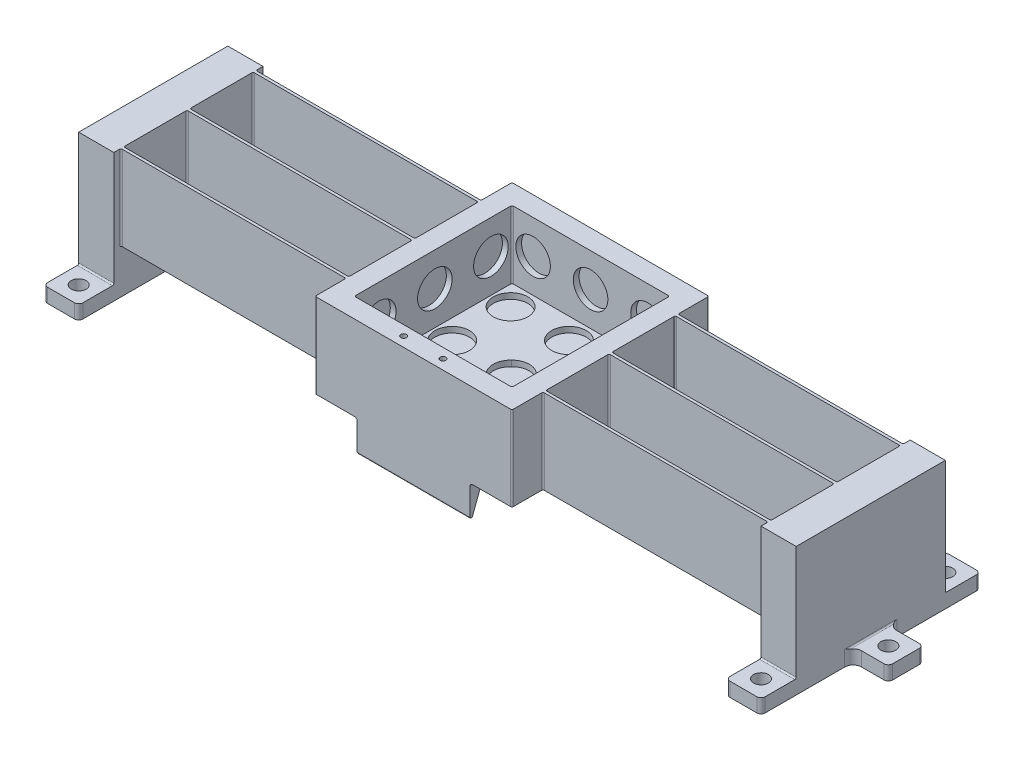
SolidWorks part; units mm, degrees
ref_plane "Front Plane" through (0, 0, 0) normal (0, 0, 1) x (1, 0, 0)
ref_plane "Top Plane" through (0, 0, 0) normal (0, 1, 0) x (1, 0, 0)
ref_plane "Right Plane" through (0, 0, 0) normal (1, 0, 0) x (0, 0, -1)
sketch "Sketch1" plane through (0, 0, 0) normal (0, 1, 0) x (1, 0, 0)
  line L1 (-35, -35) -> (35, -35)
  line L2 (-35, -35) -> (-35, 35)
  line L3 (-35, 35) -> (35, 35)
  line L4 (35, -35) -> (35, 35)
  line L5 (-35, -35) -> (35, 35) construction
  line L6 (-35, 35) -> (35, -35) construction
  point P0 (0, 0)
  dimension "D1" = 70
  dimension "D2" = 70
extrude "Boss-Extrude1" add sketch "Sketch1" along normal blind 30
shell "Shell1" thickness 7 removed face at (0, 30, 0)
sketch "Sketch2" plane through (0, 30, 0) normal (0, 1, 0) x (1, 0, 0)
  line L0 (-35, 35) -> (-35, -35) construction
  line L1 (-28, -28) -> (28, -28) construction
  line L2 (-28, -28) -> (-28, 28) construction
  line L3 (-28, 28) -> (28, 28) construction
  line L4 (28, -28) -> (28, 28) construction
  line L5 (-28, -28) -> (28, 28) construction
  line L6 (-28, 28) -> (28, -28) construction
  line L7 (35, 35) -> (-35, 35) construction
  point P0 (0, 0)
  dimension "D1" = 7
  dimension "D2" = 7
sketch "Sketch3" plane through (35, 0, 0) normal (1, 0, 0) x (0, 0, -1)
  line L0 (-35, 30) -> (35, 30) construction
  line L1 (-24, 30) -> (-23, 30)
  line L2 (-24, 30) -> (-24, 0)
  line L3 (-24, 0) -> (-23, 0)
  line L4 (-23, 30) -> (-23, 0)
  line L5 (-35, 0) -> (35, 0) construction
  line L6 (-28, 30) -> (28, 30) construction
  line L7 (-0.5, 30) -> (0.5, 30)
  line L8 (-0.5, 30) -> (-0.5, 0)
  line L9 (-0.5, 0) -> (0.5, 0)
  line L10 (0.5, 30) -> (0.5, 0)
  line L11 (28, 30) -> (-28, 30) construction
  line L12 (24, 30) -> (23, 30)
  line L13 (24, 30) -> (24, 0)
  line L14 (24, 0) -> (23, 0)
  line L15 (23, 30) -> (23, 0)
  line L16 (-23.5, 30) -> (-23.5, 0) construction
  line L17 (0, 30) -> (0, 0) construction
  line L18 (23.5, 0) -> (23.5, 30) construction
  dimension "D1" = 23
  dimension "D2" = 23
  dimension "D3" = 1
extrude "Boss-Extrude2" add sketch "Sketch3" along normal blind 80
sketch "Sketch5" plane through (115, 0, 0) normal (1, 0, 0) x (0, 0, -1)
  line L0 (-24, 30) -> (-24, 0) construction
  line L1 (-26.5, 30) -> (26.5, 30)
  line L2 (-26.5, 30) -> (-26.5, 0)
  line L3 (-26.5, 0) -> (26.5, 0)
  line L4 (26.5, 30) -> (26.5, 0)
  line L5 (28, 30) -> (-28, 30) construction
  line L6 (24, 0) -> (35, 0) construction
  line L7 (24, 0) -> (24, 30) construction
  dimension "D1" = 2.5
  dimension "D2" = 2.5
extrude "Boss-Extrude3" add sketch "Sketch5" along normal blind 12.5
sketch "Sketch6" plane through (0, 0, 0) normal (0, -1, 0) x (1, 0, 0)
  line L1 (115, 26.5) -> (127.5, 26.5)
  line L2 (115, 26.5) -> (115, -26.5)
  line L3 (115, -26.5) -> (127.5, -26.5)
  line L4 (127.5, 26.5) -> (127.5, -26.5)
extrude "Boss-Extrude4" add sketch "Sketch6" along normal blind 15.75
sketch "Sketch8" plane through (0, -15.75, 0) normal (0, -1, 0) x (1, 0, 0)
  line L1 (127.5, -26.5) -> (115, -26.5)
  line L2 (127.5, -26.5) -> (127.5, -39)
  line L3 (127.5, -39) -> (115, -39)
  line L4 (115, -26.5) -> (115, -39)
  line L5 (127.5, 26.5) -> (115, 26.5)
  line L6 (127.5, 26.5) -> (127.5, 39)
  line L7 (127.5, 39) -> (115, 39)
  line L8 (115, 26.5) -> (115, 39)
  line L13 (127.5, -26.5) -> (127.5, 26.5) construction
  line L14 (140, -6.25) -> (127.5, -6.25)
  line L15 (140, -6.25) -> (140, 6.25)
  line L16 (140, 6.25) -> (127.5, 6.25)
  line L17 (127.5, -6.25) -> (127.5, 6.25)
  line L18 (140, -6.25) -> (127.5, 6.25) construction
  line L19 (140, 6.25) -> (127.5, -6.25) construction
  line L20 (115, 0) -> (140, 0) construction
  line L21 (115, 0.5) -> (115, -0.5) construction
  point P13 (133.75, 0)
  point P19 (127.5, 0)
  point P20 (127.5, 0)
extrude "Boss-Extrude5" add sketch "Sketch8" against normal blind 5
hole_wizard "Ø5.0mm Dowel Hole1" positions "Sketch9" profile "Sketch10" hole size "Ø5.0" standard "ANSI Metric"
sketch "Sketch9" plane through (0, -10.75, 0) normal (0, 1, 0) x (1, 0, 0)
  line L0 (121.25, 39) -> (121.25, 32.75) construction
  line L1 (115, 39) -> (127.5, 39) construction
  line L2 (121.25, 32.75) -> (127.5, 32.75) construction
  line L3 (127.5, 39) -> (127.5, 26.5) construction
  line L5 (127.5, 0) -> (133.75, 0) construction
  line L6 (127.5, -6.25) -> (127.5, 6.25) construction
  line L7 (133.75, 0) -> (133.75, 6.25) construction
  line L8 (127.5, 6.25) -> (140, 6.25) construction
  line L10 (121.25, -26.5) -> (121.25, -32.75) construction
  line L11 (115, -26.5) -> (127.5, -26.5) construction
  line L12 (121.25, -32.75) -> (127.5, -32.75) construction
  line L13 (127.5, -26.5) -> (127.5, -39) construction
  point P0 (121.25, 32.75)
  point P2 (133.75, 0)
  point P4 (121.25, -32.75)
sketch "Sketch10" plane through (121.25, -10.75, -32.75) normal (1, 0, 0) x (0, 0, 1)
  line L0 (0, 0) -> (0, 18.1023)
  line L1 (0, 18.1023) -> (2.65, 16.51)
  line L2 (2.65, 16.51) -> (2.65, 0)
  line L5 (2.65, 0) -> (0, 0)
  line L10 (0, 18.1023) -> (-2.65, 16.51) construction
  line L11 (0, -6.35) -> (0, 107.95) construction
  dimension "Hole Dia." = 5.3
  dimension "Hole Depth" = 16.51
  dimension "Drill Angle" = 118
mirror "Mirror1" about plane through (0, 0, 0) normal (1, 0, 0) of "Boss-Extrude2", "Boss-Extrude3", "Boss-Extrude5", "Boss-Extrude4", "Ø5.0mm Dowel Hole1"
fillet "Fillet1" radius 0.5 30 edges at (35, 15, 23) (115, 15, 23) (35, 15, 24) (115, 15, 24) (35, 15, 0.5) (115, 15, 0.5) (35, 15, -0.5) (115, 15, -0.5) (35, 15, -23) (115, 15, -23) (35, 15, -24) (115, 15, -24) (-115, 15, 24) (-115, 15, 23) (-115, 15, 0.5) (-115, 15, -0.5) (-115, 15, -24) (-115, 15, -23) (-35, 15, 24) (-35, 15, 23) (-35, 15, 0.5) (-35, 15, -0.5) (-35, 15, -23) (-35, 15, -24) (-121.25, -10.75, -26.5) (-127.5, -10.75, 0) (-121.25, -10.75, 26.5) (121.25, -10.75, 26.5) (121.25, -10.75, -26.5) (127.5, -10.75, 0)
fillet "Fillet2" radius 1.5 12 edges at (140, -13.25, 6.25) (140, -13.25, -6.25) (127.5, -13.25, -39) (115, -13.25, -39) (127.5, -13.25, 39) (115, -13.25, 39) (-115, -13.25, -39) (-127.5, -13.25, -39) (-140, -13.25, -6.25) (-140, -13.25, 6.25) (-115, -13.25, 39) (-127.5, -13.25, 39)
sketch "Sketch11" plane through (0, 6, 0) normal (0, 1, 0) x (1, 0, 0)
  line L26 (-28, -28) -> (-28, 28) construction
  line L32 (-28, -28) -> (28, -28) construction
  circle A0 centre (-21, -21) radius 6.15
  dimension "D1" = 12.3
  dimension "D2" = 0.85
  dimension "D3" = 0.85
extrude "Cut-Extrude1" cut sketch "Sketch11" against normal blind 2.05
pattern_linear "LPattern1" count 3 spacing 20.75 along (1, 0, 0) count 3 spacing 20.75 along (0, 0, -1) of "Cut-Extrude1"
sketch "Sketch14" plane through (0, 6, 0) normal (0, 1, 0) x (1, 0, 0)
  line L0 (-28, 0) -> (0, 0) construction
  line L1 (-28, 28) -> (-28, -28) construction
  line L2 (0, 0) -> (0, -28) construction
  line L3 (-28, -28) -> (28, -28) construction
  circle A0 centre (0, 0) radius 6.15
  dimension "D1" = 12.3
extrude "Cut-Extrude4" cut sketch "Sketch14" against normal blind 2.05
sketch "Sketch12" plane through (-28, 0, 0) normal (1, 0, 0) x (0, 0, -1)
  line L5 (-28, 18) -> (-19.35, 18) construction
  line L6 (-28, 30) -> (-28, 6) construction
  circle A0 centre (-19.35, 18) radius 6.15
  dimension "D1" = 12.3
  dimension "D2" = 2.5
extrude "Cut-Extrude2" cut sketch "Sketch12" against normal blind 2.05
pattern_linear "LPattern2" count 3 spacing 19.925 along (0, 0, -1) of "Cut-Extrude2"
sketch "Sketch13" plane through (0, 0, -28) normal (0, 0, -1) x (-1, 0, 0)
  line L6 (-28, 30) -> (-28, 6) construction
  line L7 (-20.35, 18) -> (-28, 18) construction
  circle A0 centre (-20.35, 18) radius 6.15
  dimension "D1" = 12.3
  dimension "D3" = 1.5
extrude "Cut-Extrude3" cut sketch "Sketch13" along normal blind 2.05
pattern_linear "LPattern3" count 3 spacing 20.425 along (-1, 0, 0) of "Cut-Extrude3"
mirror "Mirror2" about plane through (0, 0, 0) normal (1, 0, 0) of "LPattern2", "Cut-Extrude2"
fillet "Fillet3" radius 0.5 4 edges at (28, 18, -28) (-28, 18, -28) (28, 18, 28) (-28, 18, 28)
fillet "Fillet4" radius 0.5 4 edges at (-35, 15, 35) (35, 15, 35) (-35, 15, -35) (35, 15, -35)
sketch "Sketch19" plane through (0, 0, 0) normal (1, 0, 0) x (0, 0, -1)
  line L0 (-30, 0) -> (-35, -13.25)
  line L1 (-35, -13.25) -> (-35, 0)
  line L2 (-35, 0) -> (-30, 0)
  line L3 (0, 0) -> (-30, 0) construction
  line L4 (37.5, -15.75) -> (-37.5, -15.75) construction
  dimension "D1" = 5
  dimension "D2" = 30
  dimension "D3" = 2.5
extrude "Boss-Extrude8" add sketch "Sketch19" along normal mid plane 40
sketch "Sketch20" plane through (0, 0, 0) normal (1, 0, 0) x (0, 0, -1)
  line L0 (-35, 20) -> (-42.5, 20)
  line L1 (-42.5, 20) -> (-42.5, 30)
  line L2 (-26.5, 30) -> (-42.5, 30) construction
  line L5 (-42.5, 30) -> (-40, 30)
  line L6 (-40, 30) -> (-40, 22.5)
  line L7 (-40, 22.5) -> (-35, 22.5)
  line L8 (-35, 22.5) -> (-35, 20)
  line L9 (-35, 30) -> (-35, 0) construction
  line L10 (-35, 0) -> (-35, 30) construction
  dimension "D1" = 5
  dimension "D2" = 10
  dimension "D3" = 2.5
  dimension "D4" = 2.5
extrude "Place For Sensor" [suppressed] add sketch "Sketch20" along normal mid plane 10
fillet "Place For Sensor Fillet5" [suppressed] radius 0.5
fillet "Place For Sensor Fillet6" [suppressed] radius 1.5
hole_wizard "Place For Sensor Ø3.0mm Dowel Hole2" [suppressed] positions "Sketch21" profile "Sketch22" hole size "Ø3.0" standard "ANSI Metric"
sketch "Sketch21" [suppressed] plane through (0, 0, 32.5) normal (0, 0, 1) x (1, 0, 0)
  line L0 (-2.5, 27.5) -> (2.5, 27.5) construction
  line L2 (-18, 30) -> (18, 30) construction
  line L3 (-5, 28.5) -> (-5, 20.5) construction
  line L4 (5, 28.5) -> (5, 20.5) construction
  point P0 (-2.5, 27.5)
  point P2 (2.5, 27.5)
  dimension "D1" = 2.5
  dimension "D2" = 2.5
  dimension "D3" = 2.5
sketch "Sketch22" plane through (-2.5, 27.5, 32.5) normal (1, 0, 0) x (0, -1, 0)
  line L0 (0, 0) -> (0, 2.5)
  line L1 (0, 2.5) -> (1.65, 2.5)
  line L2 (1.65, 2.5) -> (1.65, 0)
  line L5 (1.65, 0) -> (0, 0)
  line L11 (0, -6.35) -> (0, 107.95) construction
  dimension "Thru Hole Dia." = 3.3
  dimension "Thru Hole Depth" = 2.5
sketch "Sketch23" plane through (0, 30, 0) normal (0, 1, 0) x (1, 0, 0)
  line L1 (-28, -28) -> (28, -28) construction
  circle A0 centre (-7, -31.5) radius 1
  circle A1 centre (7, -31.5) radius 1
  dimension "D4" = 2
  dimension "D1" = 3.5
  dimension "D2" = 14
  dimension "D3" = 7
extrude "Cut-Extrude5" cut sketch "Sketch23" against normal blind 6
fillet "Fillet5" radius 0.5 1 edges at (0, -13.25, 35)
fillet "Fillet6" radius 1 3 edges at (-20, 0, 32.5) (20, 0, 32.5) (0, 0, 30)
fillet "Fillet8" radius 3 4 edges at (127.5, -13, 6.25) (127.5, -13, -6.25) (-127.5, -13, -6.25) (-127.5, -13, 6.25)
